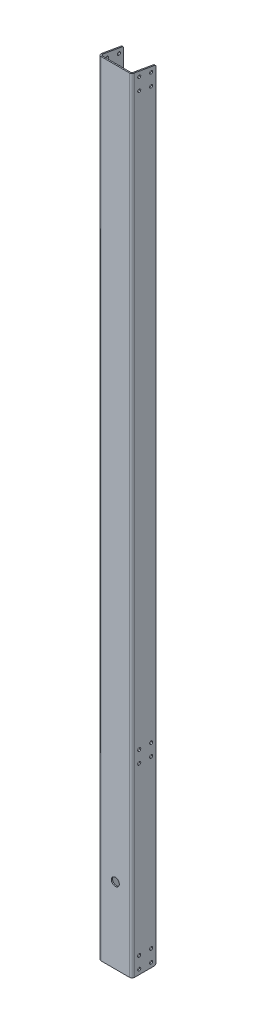
SolidWorks part; units mm, degrees
note: The reader was unsure of these and kept them because the rebuilt part matched: flange length of "Edge-Flange1", "Edge-Flange2".
ref_plane "Front Plane" through (0, 0, 0) normal (0, 0, 1) x (1, 0, 0)
ref_plane "Top Plane" through (0, 0, 0) normal (0, 1, 0) x (1, 0, 0)
ref_plane "Right Plane" through (0, 0, 0) normal (1, 0, 0) x (0, 0, -1)
sketch "Sketch1" plane through (0, 0, 0) normal (0, 0, 1) x (1, 0, 0)
  line L1 (26.6776, 624.967) -> (-26.6776, 624.967)
  line L2 (26.6776, 624.967) -> (26.6776, -624.967)
  line L3 (26.6776, -624.967) -> (-26.6776, -624.967)
  line L4 (-26.6776, 624.967) -> (-26.6776, -624.967)
  line L5 (26.6776, 624.967) -> (-26.6776, -624.967) construction
  line L6 (26.6776, -624.967) -> (-26.6776, 624.967) construction
  point P0 (0, 0)
  dimension "D1" = 53.3552
  dimension "D2" = 1249.934
base flange "Base-Flange1" sketch "Sketch1" thickness 1.8974 reverse thickness direction no parameters "D1"=2.032
edge flange "Edge-Flange1" sketch "Sketch8" flange angle 90 flange length 38.1 flange position material inside bend radius 2.032 thickness 1.8974 relief rectangular parameters "D6"=10
sketch "Sketch8" plane through (26.6776, 0, -1.8974) normal (-1, 0, 0) x (0, 1, 0)
  line L0 (624.967, 2.8778) -> (619.0909, 36.2026)
  line L2 (-624.967, 0) -> (-624.967, 36.2026)
  line L3 (-624.967, 36.2026) -> (619.0909, 36.2026)
  line L4 (624.967, 2.8778) -> (624.967, 0)
  line L5 (624.967, 0) -> (-624.967, 0) construction
  line L6 (624.967, 0) -> (-624.967, 0)
  dimension "D1" = 38.1
  dimension "D2" = 10
  dimension "D3" = 4.7752
bend "EdgeBend1" bend radius 2.032 bend angle 90 parameters "D5"=1
edge flange "Edge-Flange2" sketch "Sketch11" flange angle 90 flange length 38.1 flange position material inside bend radius 2.032 thickness 1.8974 relief rectangular parameters "D6"=10
sketch "Sketch11" plane through (-26.6776, 0, -1.8974) normal (1, 0, 0) x (0, -1, 0)
  line L0 (-624.967, 2.8778) -> (-619.0909, 36.2026)
  line L2 (-624.967, 0) -> (-624.967, 2.8778)
  line L3 (-619.0909, 36.2026) -> (624.967, 36.2026)
  line L4 (624.967, 36.2026) -> (624.967, 0)
  line L5 (624.967, 0) -> (-624.967, 0) construction
  line L6 (624.967, 0) -> (-624.967, 0)
  dimension "D1" = 10
  dimension "D2" = 4.7752
  dimension "D3" = 38.1
bend "EdgeBend2" bend radius 2.032 bend angle 90 parameters "D5"=2
fillet "Fillet1" radius 2.54 4 edges at (-25.7289, -624.967, -38.1) (25.7289, -624.967, -38.1) (-25.7289, 619.0909, -38.1) (25.7289, 619.0909, -38.1)
sketch "Sketch12" plane through (-26.6776, 0, 0) normal (-1, 0, 0) x (0, 0, 1)
  line L0 (-38.1, -622.427) -> (-38.1, 616.9596) construction
  line L1 (-3.9294, -624.967) -> (-35.56, -624.967) construction
  circle A0 centre (-30.48, -617.347) radius 2.4638
  circle A1 centre (-30.48, -598.297) radius 2.4638
  circle A2 centre (-11.43, -598.297) radius 2.4638
  circle A3 centre (-11.43, -617.347) radius 2.4638
  dimension "D1" = 4.9276
  dimension "D2" = 7.62
  dimension "D3" = 19.05
  dimension "D4" = 7.62
  dimension "D5" = 19.05
extrude "Cut-Extrude1" cut sketch "Sketch12" against normal through all normal cut yes
sketch "Sketch13" plane through (-26.6776, 0, 0) normal (-1, 0, 0) x (0, 0, 1)
  line L0 (-30.48, 612.697) -> (-11.43, 616.056) construction
  line L1 (-11.43, 616.056) -> (-11.43, 596.7122) construction
  line L2 (-11.43, 596.7122) -> (-30.48, 593.3531) construction
  line L3 (-30.48, 593.3531) -> (-30.48, 612.697) construction
  line L4 (-36.0011, 619.461) -> (-4.7752, 624.967) construction
  line L5 (-38.1, -622.427) -> (-38.1, 616.9596) construction
  circle A0 centre (-30.48, 612.697) radius 2.4638
  circle A1 centre (-11.43, 616.056) radius 2.4638
  circle A2 centre (-11.43, 596.7122) radius 2.4638
  circle A3 centre (-30.48, 593.3531) radius 2.4638
  dimension "D1" = 4.9276
  dimension "D2" = 7.62
  dimension "D3" = 19.05
  dimension "D4" = 7.62
  dimension "D5" = 19.05
extrude "Cut-Extrude2" cut sketch "Sketch13" against normal through all normal cut yes
sketch "Sketch14" plane through (26.6776, 0, 0) normal (1, 0, 0) x (0, 0, -1)
  line L0 (38.1, 616.9596) -> (38.1, -622.427) construction
  line L1 (35.56, -624.967) -> (3.9294, -624.967) construction
  circle A0 centre (11.43, -313.817) radius 2.4638
  circle A1 centre (11.43, -332.867) radius 2.4638
  circle A2 centre (30.48, -332.867) radius 2.4638
  circle A3 centre (30.48, -313.817) radius 2.4638
  dimension "D1" = 7.62
  dimension "D4" = 4.9276
  dimension "D2" = 19.05
  dimension "D3" = 19.05
  dimension "D5" = 292.1
extrude "Cut-Extrude3" cut sketch "Sketch14" against normal through all normal cut yes
hole_wizard "1/2 (0.5) Diameter Hole1" positions "Sketch15" profile "Sketch16" hole size "1/2" standard "ANSI Inch" end condition through all
sketch "Sketch15" plane through (0, 0, 0) normal (0, 0, 1) x (1, 0, 0)
  line L0 (-22.7482, -624.967) -> (22.7482, -624.967) construction
  point P0 (0, -504.317)
  point P8 (0, -624.967)
  dimension "D1" = 120.65
sketch "Sketch16" plane through (0, -504.317, 0) normal (1, 0, 0) x (0, -1, 0)
  line L0 (0, 0) -> (0, 38.1)
  line L1 (0, 38.1) -> (6.35, 38.1)
  line L2 (6.35, 38.1) -> (6.35, 0)
  line L5 (6.35, 0) -> (0, 0)
  line L11 (0, -6.35) -> (0, 107.95) construction
  dimension "Thru Hole Dia." = 12.7
  dimension "Thru Hole Depth" = 38.1
sketch "Bend-Lines1" [suppressed] plane through (0, 0, 0) normal (0, 1, 0) x (1, 0, 0)
sketch "Bounding-Box1" [suppressed] plane through (0, 0, 0) normal (0, 1, 0) x (1, 0, 0)
sheet metal parameters "Sheet-Metal1" thickness 1.8974 parameters "D1"=2.032
flat pattern "Flat-Pattern1" [suppressed]
sketch "Bend-Lines2" plane through (0, 0, 0) normal (0, 1, 0) x (1, 0, 0)
sketch3d "Bounding-Box2" [suppressed]
  line L0 (-26.6776, 508, 0) -> (-26.6776, -508, 0) construction
  line L1 (26.6776, 508, 0) -> (26.6776, -508, 0) construction
  line L2 (-26.6776, 508, 0) -> (26.6776, 508, 0) construction
  line L3 (-26.6776, -508, 0) -> (26.6776, -508, 0) construction
sheet metal parameters "Sheet-Metal2" thickness 1.8974 parameters "D1"=2.032
flat pattern "Flat-Pattern1"
sketch "Bend-Lines2" plane through (0, 0, 0) normal (0, 0, 1) x (1, 0, 0)
  line L0 (25.0893, -508) -> (25.0893, 508) construction
  line L1 (25.0893, -508) -> (25.0893, 508) construction
sketch3d "Bounding-Box2" [suppressed]
  line L0 (61.6009, 508, 0) -> (61.6009, -508, 0) construction
  line L1 (-26.6776, 508, 0) -> (-26.6776, -508, 0) construction
  line L2 (61.6009, 508, 0) -> (-26.6776, 508, 0) construction
  line L3 (61.6009, -508, 0) -> (-26.6776, -508, 0) construction
bend of the flat pattern "Flatten-<EdgeBend1>1"
sheet metal parameters "Sheet-Metal3" thickness 1.8974 parameters "D1"=2.032
flat pattern "Flat-Pattern1"
sketch "Bend-Lines2" plane through (0, 0, 0) normal (0, 0, 1) x (1, 0, 0)
  line L0 (25.0893, -508) -> (25.0893, 508) construction
  line L1 (25.0893, -508) -> (25.0893, 508) construction
  line L2 (-25.0893, 508) -> (-25.0893, -508) construction
  line L3 (-25.0893, 508) -> (-25.0893, -508) construction
sketch3d "Bounding-Box2" [suppressed]
  line L0 (61.6008, -508, 0) -> (61.6009, 513.389, 0) construction
  line L1 (-61.6009, -508, 0) -> (-61.6008, 513.389, 0) construction
  line L2 (61.6008, -508, 0) -> (-61.6009, -508, 0) construction
  line L3 (61.6009, 513.389, 0) -> (-61.6008, 513.389, 0) construction
bend of the flat pattern "Flatten-<EdgeBend1>1"
bend of the flat pattern "Flatten-<EdgeBend2>1"
sheet metal parameters "Sheet-Metal4" thickness 1.8974 parameters "D1"=2.032
flat pattern "Flat-Pattern1"
sketch "Bend-Lines2" plane through (0, 0, 0) normal (0, 0, 1) x (1, 0, 0)
  line L0 (25.0893, -508) -> (25.0893, 508) construction
  line L1 (25.0893, -508) -> (25.0893, 508) construction
  line L2 (-25.0893, 508) -> (-25.0893, -508) construction
  line L3 (-25.0893, 508) -> (-25.0893, -508) construction
sketch3d "Bounding-Box2" [suppressed]
  line L0 (61.6008, -508, 0) -> (61.6009, 513.389, 0) construction
  line L1 (-61.6009, -508, 0) -> (-61.6008, 513.389, 0) construction
  line L2 (61.6008, -508, 0) -> (-61.6009, -508, 0) construction
  line L3 (61.6009, 513.389, 0) -> (-61.6008, 513.389, 0) construction
bend of the flat pattern "Flatten-<EdgeBend1>1"
bend of the flat pattern "Flatten-<EdgeBend2>1"
sheet metal parameters "Sheet-Metal5" thickness 1.8974 parameters "D1"=2.032
flat pattern "Flat-Pattern1"
sketch "Bend-Lines2" plane through (0, 0, 0) normal (0, 0, 1) x (1, 0, 0)
  line L0 (25.0893, -590.042) -> (25.0893, 590.042) construction
  line L1 (25.0893, -590.042) -> (25.0893, 590.042) construction
  line L2 (-25.0893, 590.042) -> (-25.0893, -590.042) construction
  line L3 (-25.0893, 590.042) -> (-25.0893, -590.042) construction
sketch3d "Bounding-Box2" [suppressed]
  line L0 (61.6005, -590.042, 0) -> (61.6009, 590.042, 0) construction
  line L1 (-61.6009, -590.042, 0) -> (-61.6005, 590.042, 0) construction
  line L2 (61.6005, -590.042, 0) -> (-61.6009, -590.042, 0) construction
  line L3 (61.6009, 590.042, 0) -> (-61.6005, 590.042, 0) construction
bend of the flat pattern "Flatten-<EdgeBend1>1"
bend of the flat pattern "Flatten-<EdgeBend2>1"
sheet metal parameters "Sheet-Metal6" thickness 1.8974 parameters "D1"=2.032
flat pattern "Flat-Pattern1"
sketch "Bend-Lines2" plane through (0, 0, 0) normal (0, 0, 1) x (1, 0, 0)
  line L0 (25.0893, -624.967) -> (25.0893, 624.967) construction
  line L1 (25.0893, -624.967) -> (25.0893, 624.967) construction
  line L2 (-25.0893, 624.967) -> (-25.0893, -624.967) construction
  line L3 (-25.0893, 624.967) -> (-25.0893, -624.967) construction
sketch3d "Bounding-Box2" [suppressed]
  line L0 (61.6004, -624.967, 0) -> (61.6009, 624.967, 0) construction
  line L1 (-61.6009, -624.967, 0) -> (-61.6004, 624.967, 0) construction
  line L2 (61.6004, -624.967, 0) -> (-61.6009, -624.967, 0) construction
  line L3 (61.6009, 624.967, 0) -> (-61.6004, 624.967, 0) construction
bend of the flat pattern "Flatten-<EdgeBend1>1"
bend of the flat pattern "Flatten-<EdgeBend2>1"
sheet metal parameters "Sheet-Metal7" thickness 1.8974 parameters "D1"=2.032
flat pattern "Flat-Pattern1"
sketch "Bend-Lines2" plane through (0, 0, 0) normal (0, 0, 1) x (1, 0, 0)
  line L0 (25.0893, -624.967) -> (25.0893, 624.967) construction
  line L1 (25.0893, -624.967) -> (25.0893, 624.967) construction
  line L2 (-25.0893, 624.967) -> (-25.0893, -624.967) construction
  line L3 (-25.0893, 624.967) -> (-25.0893, -624.967) construction
sketch3d "Bounding-Box2" [suppressed]
  line L0 (61.6004, -624.967, 0) -> (61.6009, 624.967, 0) construction
  line L1 (-61.6009, -624.967, 0) -> (-61.6004, 624.967, 0) construction
  line L2 (61.6004, -624.967, 0) -> (-61.6009, -624.967, 0) construction
  line L3 (61.6009, 624.967, 0) -> (-61.6004, 624.967, 0) construction
bend of the flat pattern "Flatten-<EdgeBend1>1"
bend of the flat pattern "Flatten-<EdgeBend2>1"
